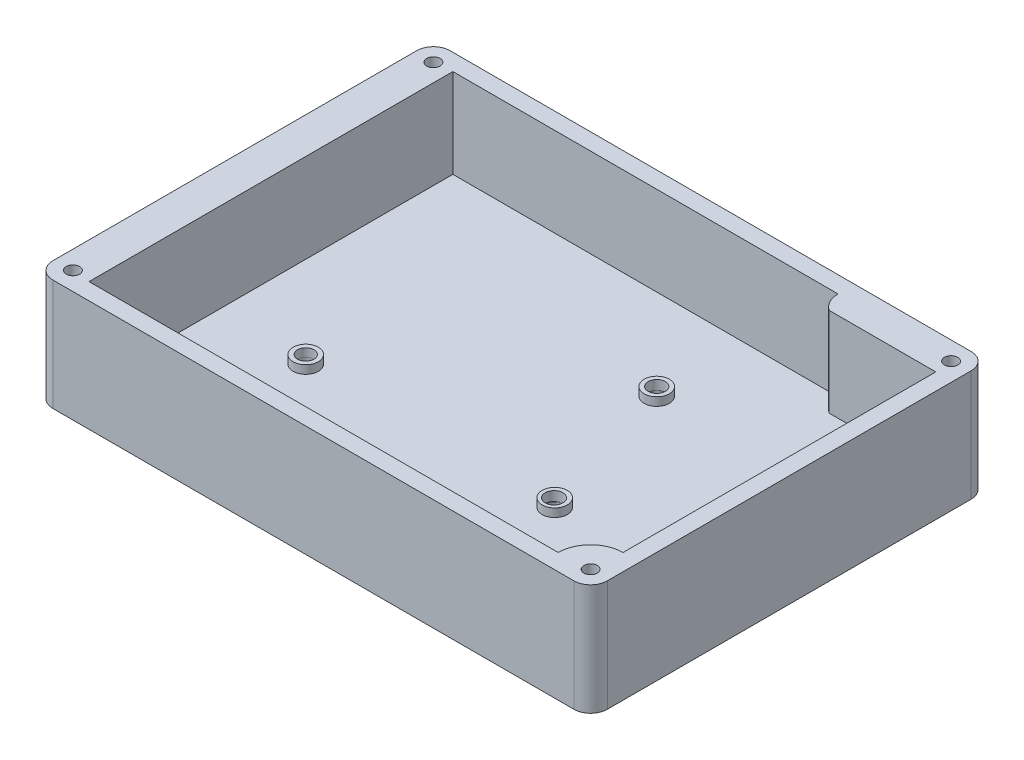
SolidWorks part; units mm, degrees
ref_plane "Front Plane" through (0, 0, 0) normal (0, 0, 1) x (1, 0, 0)
ref_plane "Top Plane" through (0, 0, 0) normal (0, 1, 0) x (1, 0, 0)
ref_plane "Right Plane" through (0, 0, 0) normal (1, 0, 0) x (0, 0, -1)
sketch "Sketch1" plane through (0, 0, 0) normal (0, 1, 0) x (1, 0, 0)
  line L0 (-48.075, 35.695) -> (-51.575, 35.695)
  line L1 (-48.075, 35.695) -> (48.075, 35.695)
  line L3 (-48.075, -35.695) -> (48.075, -35.695)
  line L4 (48.075, 35.695) -> (48.075, -35.695)
  line L5 (-48.075, 35.695) -> (48.075, -35.695) construction
  line L6 (-48.075, -35.695) -> (48.075, 35.695) construction
  line L7 (-51.575, 35.695) -> (-51.575, -35.695)
  line L8 (-51.575, -35.695) -> (-48.075, -35.695)
  point P0 (0, 0)
  dimension "D1" = 96.15
  dimension "D2" = 71.39
  dimension "D3" = 3.5
extrude "Boss-Extrude1" add sketch "Sketch1" along normal blind 20
sketch "Sketch2" plane through (0, 20, 0) normal (0, 1, 0) x (1, 0, 0)
  line L0 (48.075, -35.695) -> (48.075, 35.695) construction
  line L1 (-45.075, 32.695) -> (24.1501, 32.695)
  line L2 (-45.075, 32.695) -> (-45.075, -32.695)
  line L3 (-45.075, -32.695) -> (39.2543, -32.695)
  line L4 (45.075, 29.3419) -> (45.075, -26.8743)
  line L5 (-45.075, 32.695) -> (40.3633, -29.2774) construction
  line L6 (-45.075, -32.695) -> (40.4523, 29.3419) construction
  line L7 (48.075, 35.695) -> (-51.575, 35.695) construction
  line L9 (45.075, 29.3419) -> (25.9073, 29.3419)
  arc A1 (45.075, -26.8743) -> (39.2543, -32.695) centre (45.075, -32.695) ccw
  arc A2 (25.9073, 29.3419) -> (24.1501, 32.695) centre (28.2278, 32.695) cw
  point P0 (0, 0)
  dimension "D1" = 3
  dimension "D2" = 3
extrude "Cut-Extrude1" cut sketch "Sketch2" against normal blind 16
fillet "Fillet2" radius 3 4 edges at (-51.575, 10, -35.695) (-51.575, 10, 35.695) (48.075, 10, 35.695) (48.075, 10, -35.695)
ref_plane "Plane1" through (-1.75, 0, 0) normal (-1, 0, 0) x (0, 0, 1)
ref_plane "Plane2" through (0, 0, 0) normal (0, 0, -1) x (-1, 0, 0)
sketch "Sketch3" plane through (0, 20, 0) normal (0, 1, 0) x (1, 0, 0)
  line L0 (-48.575, -35.695) -> (45.075, -35.695) construction
  line L1 (-51.575, 32.695) -> (-51.575, -32.695) construction
  line L2 (-1.75, 11) -> (-1.75, -11) construction
  line L3 (11, 0) -> (-11, 0) construction
  circle A0 centre (-48.275, -32.395) radius 1.2
  circle A1 centre (44.775, -32.395) radius 1.2
  circle A2 centre (-48.275, 32.395) radius 1.2
  circle A3 centre (44.775, 32.395) radius 1.2
  dimension "D1" = 3.3
  dimension "D2" = 3.3
extrude "Cut-Extrude2" cut sketch "Sketch3" against normal blind 10
hole_wizard "Ø3.0mm Dowel Hole1" positions "Sketch7" profile "Sketch8" hole size "Ø3.0" standard "DIN"
sketch "Sketch7" plane through (0, 4, 0) normal (0, 1, 0) x (1, 0, 0)
  point P0 (-28.7628, -10.0573)
  point P3 (7.7497, 16.4989)
  point P5 (15.9022, -9.9727)
sketch "Sketch8" plane through (-28.7628, 4, 10.0573) normal (1, 0, 0) x (0, 0, 1)
  line L0 (0, 0) -> (0, 3.2)
  line L1 (0, 3.2) -> (1.5, 2.2987)
  line L2 (1.5, 2.2987) -> (1.5, 0)
  line L5 (1.5, 0) -> (0, 0)
  line L10 (0, 3.2) -> (-1.5, 2.2987) construction
  line L11 (0, -6.35) -> (0, 107.95) construction
  dimension "Hole Dia." = 3
  dimension "Hole Depth" = 3.2
  dimension "Drill Angle" = 118
sketch "Sketch10" plane through (0, 4, 0) normal (0, 1, 0) x (1, 0, 0)
  circle A0 centre (-28.7628, -10.0573) radius 2.2632
  circle A1 centre (15.9022, -9.9727) radius 2.2632
  circle A2 centre (7.7668, 16.4979) radius 2.2632
  dimension "D1" = 4.5265
sketch "Sketch12" plane through (0, 4, 0) normal (0, 1, 0) x (1, 0, 0)
extrude "Boss-Extrude2" add sketch "Sketch10" along normal blind 1.5
sketch "Sketch15" plane through (0, 5.5, 0) normal (0, 1, 0) x (1, 0, 0)
  circle A0 centre (-28.7628, -10.0573) radius 1.4753
  circle A1 centre (15.8626, -10.0573) radius 1.5895
  circle A2 centre (7.7668, 16.4979) radius 1.5384
extrude "Cut-Extrude3" cut sketch "Sketch15" against normal blind 1.7
